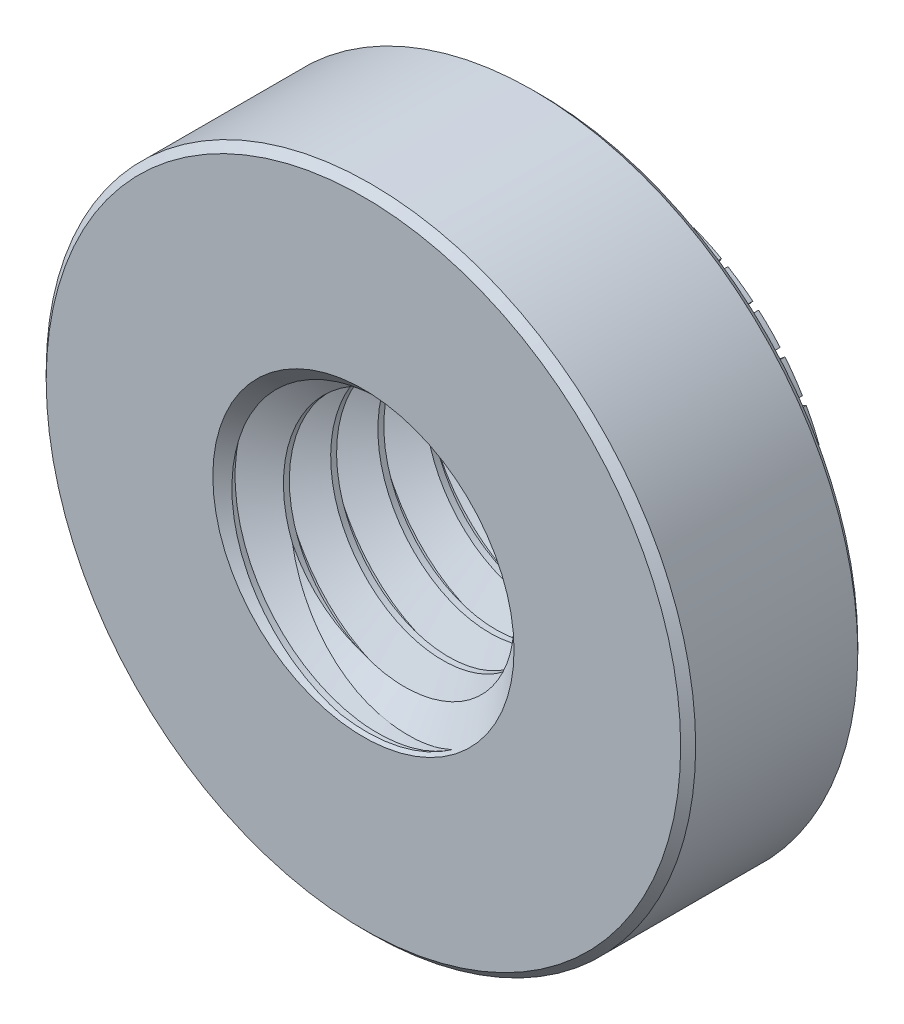
SolidWorks part; units mm, degrees
material "Brass"
ref_plane "Front Plane" through (0, 0, 0) normal (0, 0, 1) x (1, 0, 0)
ref_plane "Top Plane" through (0, 0, 0) normal (0, 1, 0) x (1, 0, 0)
ref_plane "Right Plane" through (0, 0, 0) normal (1, 0, 0) x (0, 0, -1)
sketch "Sketch1" plane through (0, 0, 0) normal (0, 0, 1) x (1, 0, 0)
  circle A0 centre (0, 0) radius 5.5
  dimension "A" = 11
extrude "Extrude1" add sketch "Sketch1" against normal blind 3
sketch "Sketch2" plane through (0, 0, -3) normal (0, 0, -1) x (-1, 0, 0)
  circle A0 centre (0, 0) radius 3.685
  dimension "C" = 7.37
extrude "Extrude2" add sketch "Sketch2" along normal blind 1.53
sketch "Sketch3" plane through (0, 0, -4.53) normal (0, 0, -1) x (-1, 0, 0)
  line L0 (0, 3.4945) -> (0, 5.5)
  circle A1 centre (0, 0) radius 5.5 construction
  circle A2 centre (0, 0) radius 3.4945
  circle A3 centre (0, 0) radius 3.4945 construction
  dimension "D1" = 0.1905
extrude "Cut-Extrude-Thin1" cut sketch "Sketch3" against normal up to surface (1.53 mm away) thin up to face at (5.5, 0, -3) thin type mid plane wall 0.127
pattern_circular "CirPattern1" count 36 over 360 about axis through (0, 0, 0) along (0, 0, 1) of "Cut-Extrude-Thin1"
sketch "Sketch5" plane through (0, 0, -4.53) normal (0, 0, -1) x (-1, 0, 0)
  circle A2 centre (0, 0) radius 3.2405
  circle A3 centre (0, 0) radius 3.2405
  dimension "D1" = 0.254
extrude "Cut-Extrude1" cut sketch "Sketch5" against normal blind 0.254 flip side to cut
chamfer "Chamfer1" distance 0.127 angle 45 1 edges at (-3.2405, 0, -4.53)
sketch "Sketch6" plane through (0, 0, -3) normal (0, 0, -1) x (-1, 0, 0)
  circle A0 centre (0, 0) radius 3.2405 construction
  circle A1 centre (0, 0) radius 3.2405
  circle A2 centre (0, 0) radius 5.5 construction
  circle A3 centre (0, 0) radius 5.5
extrude "Cut-Extrude2" cut sketch "Sketch6" along normal blind 0.127
chamfer "Chamfer2" distance 0.127 angle 45 2 edges at (5.5, 0, 0) (5.5, 0, -3)
sketch "Sketch7" plane through (0, 0, 0) normal (0, 0, 1) x (1, 0, 0)
  circle A0 centre (0, 0) radius 2.5
  dimension "Thread Od" = 5
extrude "Cut-Extrude3" cut sketch "Sketch7" against normal through all
sketch "Sketch8" plane through (0, 0, -4.53) normal (0, 0, -1) x (-1, 0, 0)
  circle A0 centre (0, 0) radius 2.5 construction
  circle A1 centre (0, 0) radius 2.5
curve "Helix/Spiral1" pitch 0.8 height 6 turns 7.5 parameters "pitch"=0.8
sketch "Sketch9" plane through (0, 0, 0) normal (1, 0, 0) x (0, 0, -1)
  line L0 (5.23, 2.5) -> (4.93, 1.9804)
  line L1 (4.93, 1.9804) -> (4.83, 1.9804)
  line L2 (4.83, 1.9804) -> (4.53, 2.5)
  line L3 (5.23, 2.5) -> (4.53, 2.5)
  line L4 (4.88, 2.5) -> (4.88, 1.9804) construction
  line L5 (5.08, 2.2402) -> (4.68, 2.2402) construction
  line L6 (4.53, -2.5) -> (4.53, 2.5) construction
  dimension "D1" = 60
  dimension "D2" = 0.1
  dimension "D3" = 0.4
sweep "Sweep1" add profiles "Sketch9" path "Helix/Spiral1"
sketch "Sketch10" plane through (0, 0, 0) normal (0, 0, 1) x (1, 0, 0)
  circle A1 centre (0, 0) radius 5.373
  circle A2 centre (0, 0) radius 5.373
  dimension "D1" = 0
extrude "Cut-Extrude4" cut sketch "Sketch10" along normal through all
sketch "Sketch11" plane through (0, 0, -4.53) normal (0, 0, -1) x (-1, 0, 0)
  circle A0 centre (0, 0) radius 3.1135 construction
  circle A1 centre (0, 0) radius 3.1135
extrude "Cut-Extrude5" cut sketch "Sketch11" along normal through all
sketch "Sketch13" plane through (0, 0, 0) normal (0, 0, 1) x (1, 0, 0)
  circle A2 centre (0, 0) radius 2.5508
  circle A3 centre (0, 0) radius 2.5508
  dimension "D1" = 0.0508
extrude "Cut-Extrude6" cut sketch "Sketch13" against normal through all draft 45
sketch "Sketch14" plane through (0, 0, -4.53) normal (0, 0, -1) x (-1, 0, 0)
  circle A2 centre (0, 0) radius 2.5508
  circle A3 centre (0, 0) radius 2.5508
  dimension "D1" = 0.0508
extrude "Cut-Extrude7" cut sketch "Sketch14" against normal through all draft 45
equation "\"D3@Helix/Spiral1\" = \"B@Extrude1\"+3"
equation "\"D2@Sketch9\" = \"pitch@Helix/Spiral1\"*.125"
equation "\"D3@Sketch9\" = \"pitch@Helix/Spiral1\"*.50"
